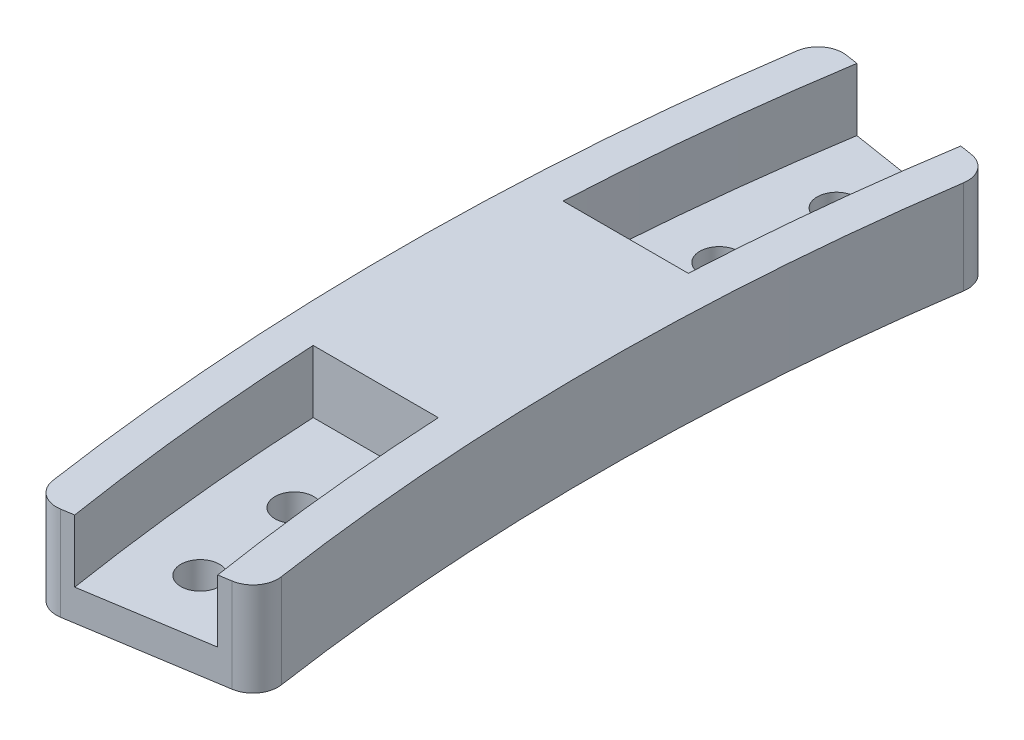
SolidWorks part; units mm, degrees
ref_plane "Front Plane" through (0, 0, 0) normal (0, 0, 1) x (1, 0, 0)
ref_plane "Top Plane" through (0, 0, 0) normal (0, 1, 0) x (1, 0, 0)
ref_plane "Right Plane" through (0, 0, 0) normal (1, 0, 0) x (0, 0, -1)
sketch "Sketch1" plane through (0, 0, 0) normal (0, 1, 0) x (1, 0, 0)
  line L0 (0, 0) -> (-197.5377, -31.2869) construction
  line L1 (0, 0) -> (-197.5377, 31.2869) construction
  line L2 (0, 0) -> (-195, 0) construction
  line L3 (-197.5377, 31.2869) -> (-187.6608, 29.7225)
  line L4 (-187.6608, -29.7225) -> (-197.5377, -31.2869)
  line L5 (0, 0) -> (-200.5007, -31.7562) construction
  line L6 (0, 0) -> (-200.5007, 31.7562) construction
  line L7 (-200.5007, 31.7562) -> (-184.6977, 29.2532)
  line L8 (-200.5007, -31.7562) -> (-184.6977, -29.2532)
  arc A0 (-197.5377, 31.2869) -> (-197.5377, -31.2869) centre (0, 0) ccw
  arc A1 (-187.6608, 29.7225) -> (-187.6608, -29.7225) centre (0, 0) ccw
  arc A2 (-192.5992, -30.5047) -> (-192.5992, 30.5047) centre (0, 0) cw construction
  arc A4 (-184.6977, 29.2532) -> (-184.6977, -29.2532) centre (0, 0) ccw
  arc A5 (-200.5007, 31.7562) -> (-200.5007, -31.7562) centre (0, 0) ccw
  dimension "D1" = 200
  dimension "D2" = 190
  dimension "D3" = 5
  dimension "D5" = 187
  dimension "D6" = 203
  dimension "D4" = 18
extrude "Boss-Extrude1" add sketch "Sketch1" along normal blind 10 contours A1 L3 A0 L4 | L7 A5 L8 A0 | A4 L7 A1 L8 region at (-200.6761, 0, 0) region at (-194.2416, 0, 0) region at (-187.7297, 0, 0)
ref_plane "Plane1" through (-195, 0, 0) normal (1, 0, 0) x (0, 0, -1)
sketch "Sketch15" plane through (0, 10, 0) normal (0, 1, 0) x (1, 0, 0)
  line L0 (-187.6608, -29.7225) -> (-197.5377, -31.2869) construction
  line L1 (-185, 10) -> (-205, 10)
  line L2 (-185, 10) -> (-185, -10)
  line L3 (-185, -10) -> (-205, -10)
  line L4 (-205, 10) -> (-205, -10)
  line L5 (-185, 10) -> (-205, -10) construction
  line L6 (-185, -10) -> (-205, 10) construction
  line L7 (-197.5377, 31.2869) -> (-187.6608, 29.7225) construction
  line L8 (-187.6608, -29.7225) -> (-197.5377, -31.2869)
  line L9 (-197.5377, 31.2869) -> (-187.6608, 29.7225)
  arc A2 (-187.6608, 29.7225) -> (-187.6608, -29.7225) centre (0, 0) ccw construction
  arc A3 (-197.5377, 31.2869) -> (-197.5377, -31.2869) centre (0, 0) ccw construction
  arc A4 (-187.6608, 29.7225) -> (-187.6608, -29.7225) centre (0, 0) ccw
  arc A5 (-197.5377, 31.2869) -> (-197.5377, -31.2869) centre (0, 0) ccw
  point P0 (-195, 0)
  line M5 (-200.5007, -31.7562) -> (-184.6977, -29.2532)
  line M7 (-184.6977, 29.2532) -> (-200.5007, 31.7562)
  dimension "D1" = 20
  dimension "D2" = 20
extrude "Cut-Extrude1" cut sketch "Sketch15" against normal blind 5 contours A5 L1 A4 M7 | L3 A5 A4 M5 region at (-193.9153, 10, -20.2762) region at (-193.9153, 10, 20.2762)
ref_plane "Plane2" through (-195, 0, 0) normal (-1, 0, 0) x (0, 0, 1)
sketch "Sketch12" plane through (0, 0, 0) normal (0, 1, 0) x (1, 0, 0)
  line L0 (0, 0) -> (-194.258, -16.9954) construction
  line L1 (0, 0) -> (-193.3317, -25.4526) construction
  line L2 (0, 0) -> (-195, 0) construction
  line L3 (0, 0) -> (-195, 0) construction
  line L4 (0, 0) -> (-194.258, 16.9954) construction
  line L5 (0, 0) -> (-193.3317, 25.4526) construction
  arc A0 (-192.5992, 30.5047) -> (-192.5992, -30.5047) centre (0, 0) ccw construction
  dimension "D1" = 10
  dimension "D2" = 15
hole_wizard "Ø3.1 (3.1) Diameter Hole2" positions "Sketch18" profile "Sketch17" hole size "Ø3.1" standard "ISO" end condition through all
sketch "Sketch18" plane through (0, 0, 0) normal (0, -1, 0) x (-1, 0, 0)
  point P0 (193.3317, -25.4526)
  point P3 (194.258, -16.9954)
  point P6 (194.258, 16.9954)
  point P9 (193.3317, 25.4526)
sketch "Sketch17" plane through (-193.3317, 0, 25.4526) normal (1, 0, 0) x (0, 0, -1)
  line L0 (0, 0) -> (0, 10)
  line L1 (0, 10) -> (1.55, 10)
  line L2 (1.55, 10) -> (1.55, 0)
  line L5 (1.55, 0) -> (0, 0)
  line L11 (0, -6.35) -> (0, 107.95) construction
  dimension "Thru Hole Dia." = 3.1
  dimension "Thru Hole Depth" = 10
fillet "Fillet1" radius 2 4 edges at (-200.5007, 5, -31.7562) (-184.6977, 5, -29.2532) (-200.5007, 5, 31.7562) (-184.6977, 5, 29.2532)
sketch "Sketch19" plane through (0, 0, 0) normal (0, -1, 0) x (1, 0, 0)
  line L2 (-198.5155, -31.4418) -> (-186.6626, -29.5645)
  line L3 (-186.6626, 29.5645) -> (-198.5155, 31.4418)
  line L4 (-198.5155, -31.4418) -> (-186.6626, -29.5645)
  line L5 (-186.6626, 29.5645) -> (-198.5155, 31.4418)
  arc A6 (-200.8068, 29.7596) -> (-200.8068, -29.7596) centre (0, 0) ccw
  arc A7 (-200.8068, -29.7596) -> (-198.5155, -31.4418) centre (-198.8284, -29.4664) ccw
  arc A8 (-186.6626, -29.5645) -> (-184.9969, -27.2971) centre (-186.9755, -27.5891) ccw
  arc A9 (-184.9969, 27.2971) -> (-184.9969, -27.2971) centre (0, 0) ccw
  arc A10 (-184.9969, 27.2971) -> (-186.6626, 29.5645) centre (-186.9755, 27.5891) ccw
  arc A11 (-198.5155, 31.4418) -> (-200.8068, 29.7596) centre (-198.8284, 29.4664) ccw
  arc A12 (-200.8068, 29.7596) -> (-200.8068, -29.7596) centre (0, 0) ccw
  arc A13 (-200.8068, -29.7596) -> (-198.5155, -31.4418) centre (-198.8284, -29.4664) ccw
  arc A14 (-186.6626, -29.5645) -> (-184.9969, -27.2971) centre (-186.9755, -27.5891) ccw
  arc A15 (-184.9969, 27.2971) -> (-184.9969, -27.2971) centre (0, 0) ccw
  arc A16 (-184.9969, 27.2971) -> (-186.6626, 29.5645) centre (-186.9755, 27.5891) ccw
  arc A17 (-198.5155, 31.4418) -> (-200.8068, 29.7596) centre (-198.8284, 29.4664) ccw
  dimension "D1" = 0
extrude "Cut-Extrude2" cut sketch "Sketch19" against normal blind 2.5
